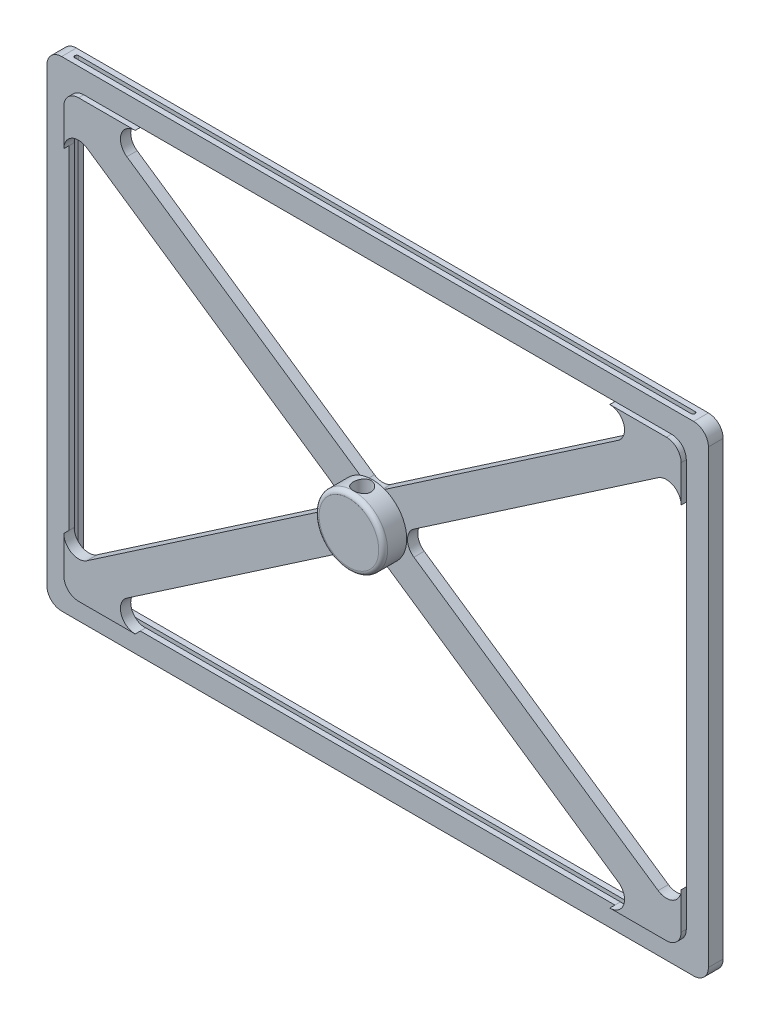
SolidWorks part; units mm, degrees
ref_plane "Front Plane" through (0, 0, 0) normal (0, 0, 1) x (1, 0, 0)
ref_plane "Top Plane" through (0, 0, 0) normal (0, 1, 0) x (1, 0, 0)
ref_plane "Right Plane" through (0, 0, 0) normal (1, 0, 0) x (0, 0, -1)
sketch "Sketch1" plane through (0, 0, 0) normal (0, 0, 1) x (1, 0, 0)
  line L14 (-209.5, 148) -> (209.5, 148)
  line L21 (-209.5, 148) -> (-209.5, -148)
  line L22 (-209.5, -148) -> (209.5, -148)
  line L23 (209.5, 148) -> (209.5, -148)
  line L24 (-209.5, 148) -> (209.5, -148) construction
  line L25 (-209.5, -148) -> (209.5, 148) construction
  line L26 (-224.5, 163) -> (224.5, 163)
  line L27 (-224.5, 163) -> (-224.5, -163)
  line L28 (-224.5, -163) -> (224.5, -163)
  line L29 (224.5, 163) -> (224.5, -163)
  line L30 (-224.5, 163) -> (224.5, -163) construction
  line L31 (-224.5, -163) -> (224.5, 163) construction
  point P0 (0, 0)
  point P5 (0, 0)
  dimension "D1" = 296
  dimension "D2" = 419
  dimension "D3" = 326
  dimension "D4" = 449
extrude "Boss-Extrude3" add sketch "Sketch1" along normal mid plane 10 contours L14 L23 L22 L21 | L26 L29 L28 L27
ref_plane "Plane1" through (0, 163, 0) normal (0, 1, 0) x (1, 0, 0)
sketch "Sketch4" plane through (0, 163, 0) normal (0, 1, 0) x (1, 0, 0)
  line L1 (-210.5, 1.3) -> (210.5, 1.3)
  line L2 (-210.5, 1.3) -> (-210.5, -1.3)
  line L3 (-210.5, -1.3) -> (210.5, -1.3)
  line L4 (210.5, 1.3) -> (210.5, -1.3)
  line L5 (-210.5, 1.3) -> (210.5, -1.3) construction
  line L6 (-210.5, -1.3) -> (210.5, 1.3) construction
  point P0 (0, 0)
  dimension "D1" = 421
  dimension "D2" = 2.6
extrude "Cut-Extrude5" cut sketch "Sketch4" against normal blind 316 contours L1 L4 L3 L2
ref_plane "Plane2" through (0, 0, 5) normal (0, 0, 1) x (1, 0, 0)
sketch "Sketch5" plane through (0, 0, 5) normal (0, 0, 1) x (1, 0, 0)
  line L0 (-209.5, -132) -> (-209.5, -148)
  line L1 (-209.5, -148) -> (-193.5, -148)
  line L2 (209.5, -132) -> (209.5, -148)
  line L3 (-209.5, 148) -> (209.5, 148) construction
  line L4 (-193.5, 148) -> (0, 16)
  line L5 (0, 16) -> (193.5, 148)
  line L6 (209.5, 132) -> (16, 0)
  line L7 (209.5, 148) -> (209.5, -148) construction
  line L8 (16, 0) -> (209.5, -132)
  line L9 (-209.5, 132) -> (-16, 0)
  line L10 (-209.5, 148) -> (-209.5, -148) construction
  line L11 (-16, 0) -> (-209.5, -132)
  line L12 (-193.5, -148) -> (0, -16)
  line L13 (-209.5, -148) -> (209.5, -148) construction
  line L14 (0, -16) -> (193.5, -148)
  line L15 (209.5, -148) -> (193.5, -148)
  line L16 (193.5, 148) -> (209.5, 148)
  line L17 (209.5, 148) -> (209.5, 132)
  line L18 (-209.5, 132) -> (-209.5, 148)
  line L19 (-209.5, 148) -> (-193.5, 148)
  dimension "D1" = 16
  dimension "D2" = 16
  dimension "D3" = 16
  dimension "D4" = 16
  dimension "D5" = 16
  dimension "D6" = 16
  dimension "D7" = 16
  dimension "D8" = 16
  dimension "D9" = 16
  dimension "D10" = 16
  dimension "D12" = 16
  dimension "D13" = 16
extrude "Boss-Extrude5" add sketch "Sketch5" along normal mid plane 7 contours L6 L8 L2 L15 L14 L12 L1 L0 L11 L9 L18 L19 L4 L5 L16 L17
fillet "Fillet1" radius 10 1 edges at (0, 16, 5) type face fillet first side face at (116.1, 95.2, 5) second side face at (-116.1, 95.2, 5)
fillet "Fillet2" radius 10 1 edges at (16, 0, 5) type face fillet first side face at (132.1, 79.2, 5) second side face at (132.1, -79.2, 5)
fillet "Fillet3" radius 10 1 edges at (-16, 0, 5) type face fillet first side face at (-132.1, 79.2, 5) second side face at (-132.1, -79.2, 5)
fillet "Fillet4" radius 10 1 edges at (0, -16, 5) type face fillet first side face at (116.1, -95.2, 5) second side face at (-116.1, -95.2, 5)
fillet "Fillet5" radius 10 1 edges at (-193.5, -148, 3.25) type face fillet first side face at (-118.3541, -96.7377, 5) second side face at (0, -148, 2.325) second side face at (0, -148, -3.15)
fillet "Fillet6" radius 10 1 edges at (-209.5, -148, 6.75) type face fillet first side face at (-185.2979, -148, 7.1875) second side face at (-209.5, -140, 6.75)
fillet "Fillet9" radius 10 1 edges at (193.5, -148, 3.25) type face fillet first side face at (118.3541, -96.7377, 5) second side face at (8.1011, -148, 2.325)
fillet "Fillet10" radius 10 1 edges at (209.5, -148, 6.75) type face fillet first side face at (209.5, -140, 6.75) second side face at (185.2979, -148, 6.3125)
fillet "Fillet11" radius 10 1 edges at (209.5, -132, 3.25) type face fillet first side face at (136.9439, -82.5044, 5) second side face at (209.5, 0, 2.325)
fillet "Fillet12" radius 10 1 edges at (-209.5, -132, 3.25) type face fillet first side face at (-136.9439, -82.5044, 5) second side face at (-209.5, 0, 2.325)
fillet "Fillet13" radius 10 1 edges at (-193.5, 148, 3.25) type face fillet first side face at (-118.3541, 96.7377, 5) second side face at (0, 148, 2.325)
fillet "Fillet14" radius 10 1 edges at (-209.5, 132, 3.25) type face fillet first side face at (-136.9439, 82.5044, 5) second side face at (-209.5, 4.7317, 2.325)
fillet "Fillet15" radius 10 1 edges at (-209.5, 148, 6.75) type face fillet first side face at (-185.2979, 148, 6.3125) second side face at (-209.5, 130.5366, 7.1875)
fillet "Fillet16" radius 10 1 edges at (209.5, 132, 3.25) type face fillet first side face at (136.9439, 82.5044, 5) second side face at (209.5, 4.7317, 2.325)
fillet "Fillet17" radius 10 1 edges at (193.5, 148, 3.25) type face fillet first side face at (118.3541, 96.7377, 5) second side face at (8.1011, 148, 2.325)
fillet "Fillet18" radius 10 1 edges at (209.5, 148, 6.75) type face fillet first side face at (185.2979, 148, 7.1875) second side face at (209.5, 130.5366, 6.3125)
fillet "Fillet19" 2 edges at (-210.5, 5, -1.3) (-210.5, 5, 1.3) type full round first side face at (0, 0, -1.3) second side face at (0, 0, 1.3) middle face at (-210.5, 5, 0)
fillet "Fillet20" 2 edges at (210.5, 5, -1.3) (210.5, 5, 1.3) type full round first side face at (0.4, 2.5, -1.3) second side face at (0.4, 2.5, 1.3) middle face at (210.5, 5, 0)
fillet "Fillet21" radius 10 1 edges at (-224.5, 163, 0) type face fillet first side face at (0, 163, 0) second side face at (-224.5, 0, 0)
fillet "Fillet22" radius 10 1 edges at (-224.5, -163, 0) type face fillet first side face at (0, -163, 0) second side face at (-224.5, -5, 0)
fillet "Fillet23" radius 10 1 edges at (224.5, -163, 0) type face fillet first side face at (224.5, 0, 0) second side face at (5, -163, 0)
fillet "Fillet24" radius 10 1 edges at (224.5, 163, 0) type face fillet first side face at (0, 163, 0) second side face at (224.5, 5, 0)
ref_plane "Plane3" through (0, 0, 8.5) normal (0, 0, 1) x (1, 0, 0)
sketch "Sketch8" plane through (0, 0, 8.5) normal (0, 0, 1) x (1, 0, 0)
  circle A0 centre (0, 0) radius 23.2567
extrude "Boss-Extrude7" add sketch "Sketch8" along normal blind 16
ref_plane "Plane4" through (0, 23.2567, 0) normal (0, 1, 0) x (1, 0, 0)
fillet "Fillet26" radius 3 1 edges at (23.2567, 0, 24.5) type face fillet first side face at (23.2567, 0, 24.5) second side face at (23.2567, 0, 24.5)
sketch "Sketch9" plane through (0, 23.2567, 0) normal (0, 1, 0) x (1, 0, 0)
  line L0 (23.2567, -21.5) -> (-23.2567, -21.5) construction
  circle A0 centre (0, -15.5) radius 6
  dimension "D1" = 12
  dimension "D2" = 6
extrude "Cut-Extrude6" cut sketch "Sketch9" against normal through all both and the other way through all contours A0
